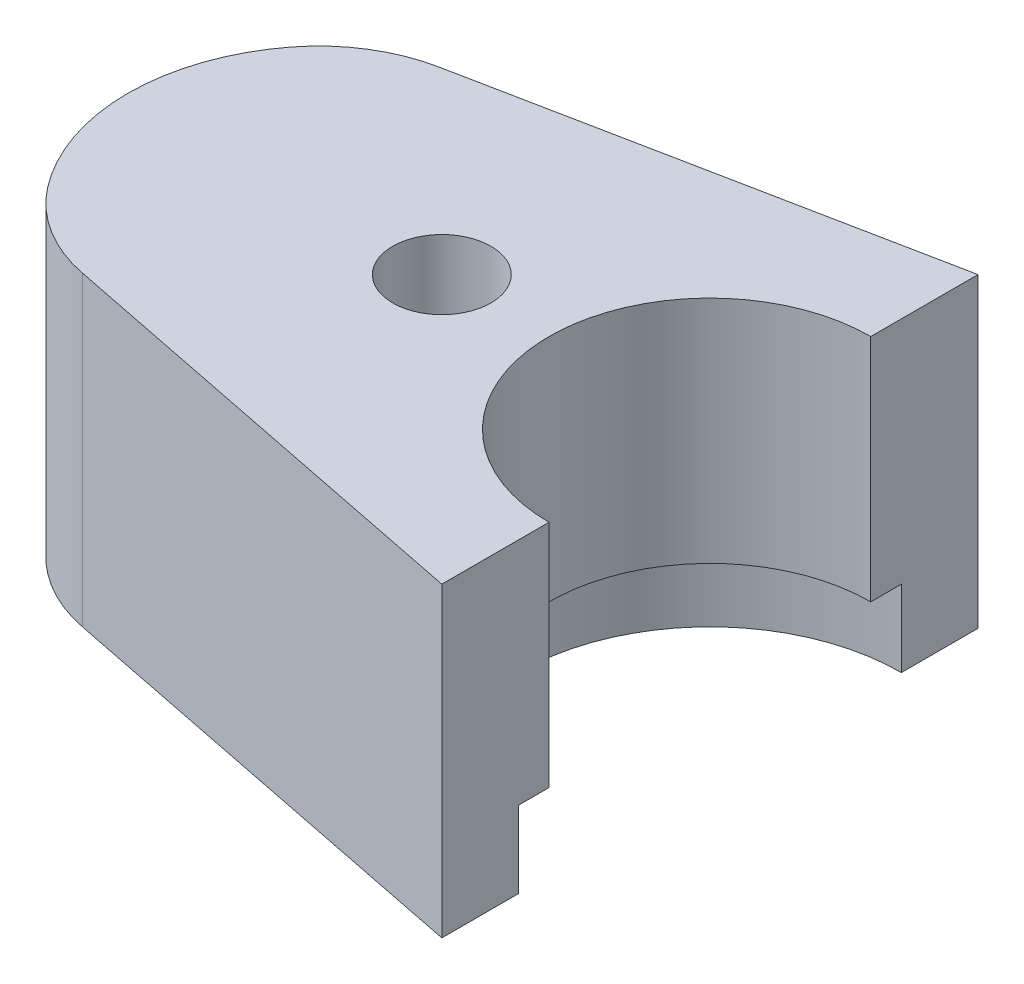
SolidWorks part; units mm, degrees
ref_plane "Front Plane" through (0, 0, 0) normal (0, 0, 1) x (1, 0, 0)
ref_plane "Top Plane" through (0, 0, 0) normal (0, 1, 0) x (1, 0, 0)
ref_plane "Right Plane" through (0, 0, 0) normal (1, 0, 0) x (0, 0, -1)
sketch "Sketch1" plane through (0, 0, 0) normal (0, 1, 0) x (1, 0, 0)
  line L0 (-0.1139, 1.9772) -> (-1.25, 1.7502)
  line L1 (-0.1139, -1.9772) -> (-1.25, -1.7502)
  line L2 (-1.25, 1.25) -> (-1.25, 1.7502)
  line L3 (-1.25, -1.25) -> (-1.25, -1.7502)
  line L4 (-1.25, -1.7502) -> (-4.1832, -1.1642)
  line L5 (-1.25, 1.7502) -> (-4.1832, 1.1642)
  line L6 (-1.25, 1.25) -> (-1.25, 1.05)
  line L7 (-1.25, -1.25) -> (-1.25, -1.05)
  circle A0 centre (-1.25, 0) radius 1.25
  circle A1 centre (-1.25, 0) radius 1.05
  arc A2 (0.1641, 1.9933) -> (0.1641, -1.9933) centre (0, 0) cw
  arc A3 (-0.1139, -1.9772) -> (0.1641, -1.9933) centre (0.0821, -0.9966) ccw
  arc A4 (-4.7783, 0.7954) -> (-4.7783, -0.7954) centre (-3.75, 0) ccw
  arc A5 (0.1641, 1.9933) -> (-0.1139, 1.9772) centre (0.0821, 0.9966) ccw
  arc A6 (-4.1832, 1.1642) -> (-4.7783, 0.7954) centre (-3.9873, 0.1835) ccw
  arc A7 (-4.1832, -1.1642) -> (-4.7783, -0.7954) centre (-3.9873, -0.1835) cw
  circle A8 centre (-3, 0) radius 0.3207
  circle A9 centre (0.5, 0) radius 0.3207
  point P12 (-3, 0)
  point P20 (0.5, 0)
extrude "Boss-Extrude1" add sketch "Sketch1" along normal blind 0.5 contours A7 L4 L3 A0 L2 L5 A6 A4 A8 region at (-1.3017, 0, -1.5001)
extrude "Boss-Extrude3" add sketch "Sketch1<20>" along normal blind 1.5 from offset 0.5 contours A1 L6 A0 L7 | A7 L4 L3 A0 L2 L5 A6 A4 A8 region at (-1.3017, 0, -1.5001) region at (-1.278, 0, -1.15)
sketch "Sketch1<20>" plane through (0, 0, 0) normal (0, 1, 0) x (1, 0, 0) same geometry as "Sketch1"
